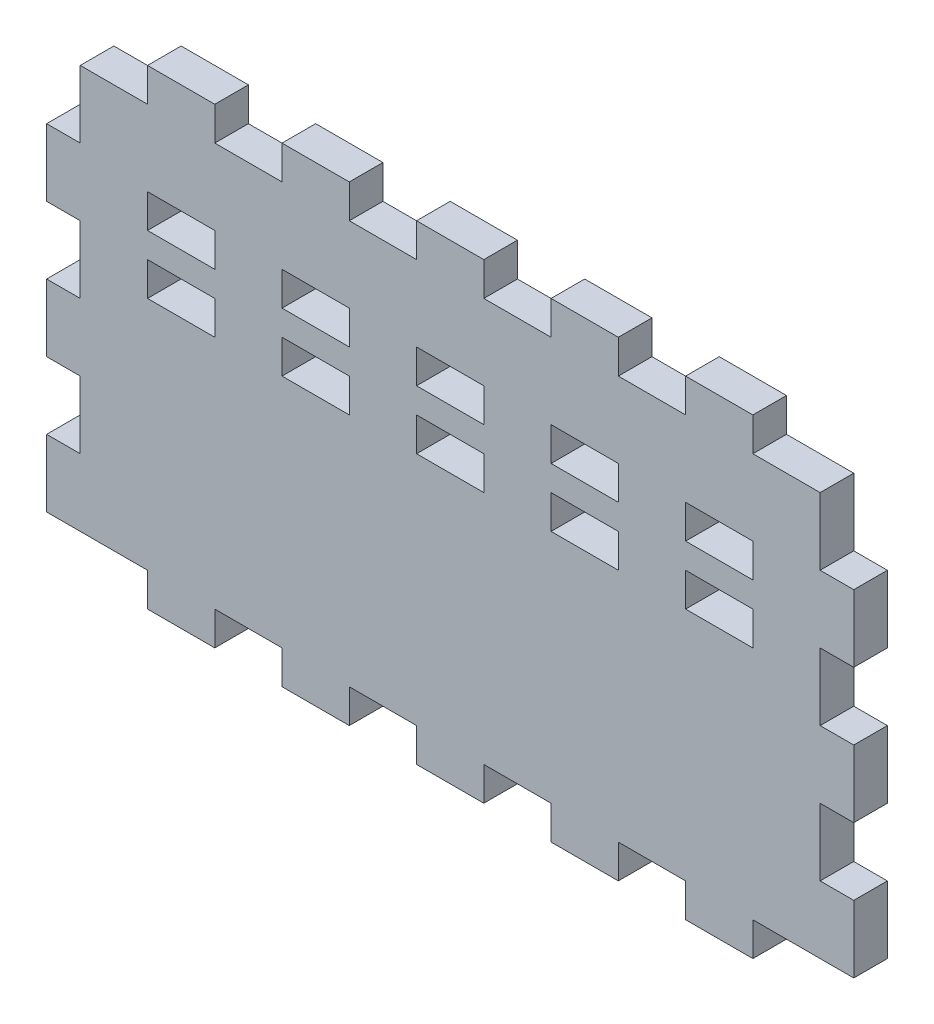
SolidWorks part; units mm, degrees
ref_plane "Front Plane" through (0, 0, 0) normal (0, 0, 1) x (1, 0, 0)
ref_plane "Top Plane" through (0, 0, 0) normal (0, 1, 0) x (1, 0, 0)
ref_plane "Right Plane" through (0, 0, 0) normal (1, 0, 0) x (0, 0, -1)
sketch "Sketch1" plane through (0, 0, 0) normal (0, 0, 1) x (1, 0, 0)
  line L1 (-139.7, -76.2) -> (139.7, -76.2)
  line L2 (-139.7, -76.2) -> (-139.7, 76.2)
  line L3 (-139.7, 76.2) -> (139.7, 76.2)
  line L4 (139.7, -76.2) -> (139.7, 76.2)
  line L5 (-139.7, -76.2) -> (139.7, 76.2) construction
  line L6 (-139.7, 76.2) -> (139.7, -76.2) construction
  point P0 (0, 0)
  dimension "D1" = 279.4
  dimension "D2" = 152.4
extrude "Boss-Extrude1" add sketch "Sketch1" along normal blind 12.7
sketch "Sketch2" plane through (0, -76.2, 0) normal (0, -1, 0) x (1, 0, 0)
  line L0 (-139.7, 0) -> (139.7, 0) construction
  line L1 (-114.3, 0) -> (-88.9, 0)
  line L2 (-114.3, 0) -> (-114.3, 12.7)
  line L3 (-114.3, 12.7) -> (-88.9, 12.7)
  line L4 (-88.9, 0) -> (-88.9, 12.7)
  line L5 (-139.7, 12.7) -> (139.7, 12.7) construction
  line L6 (-139.7, 12.7) -> (-139.7, 0) construction
  dimension "D1" = 25.4
  dimension "D2" = 25.4
extrude "Boss-Extrude2" add sketch "Sketch2" along normal blind 12.7
pattern_linear "LPattern1" count 5 spacing 50.8 along (1, 0, 0) of "Boss-Extrude2"
mirror "Mirror1" about plane through (0, 0, 0) normal (0, 1, 0) of "LPattern1"
sketch "Sketch3" plane through (139.7, 0, 0) normal (1, 0, 0) x (0, 0, -1)
  line L0 (0, 83.82) -> (0, -83.82) construction
  line L1 (-12.7, -76.2) -> (0, -76.2)
  line L2 (-12.7, -76.2) -> (-12.7, -50.8)
  line L3 (-12.7, -50.8) -> (0, -50.8)
  line L4 (0, -76.2) -> (0, -50.8)
  dimension "D1" = 25.4
extrude "Boss-Extrude3" add sketch "Sketch3" along normal blind 12.7
pattern_linear "LPattern2" count 3 spacing 50.8 along (0, 1, 0) of "Boss-Extrude3"
mirror "Mirror2" about plane through (0, 0, 0) normal (1, 0, 0) of "LPattern2"
sketch "Sketch4" plane through (0, 0, 12.7) normal (0, 0, 1) x (1, 0, 0)
  line L0 (-139.7, 25.4) -> (-139.7, 0) construction
  line L1 (-88.9, 12.7) -> (-114.3, 12.7)
  line L2 (-88.9, 12.7) -> (-88.9, 25.4)
  line L3 (-88.9, 25.4) -> (-114.3, 25.4)
  line L4 (-114.3, 12.7) -> (-114.3, 25.4)
  line L5 (-88.9, -76.2) -> (-63.5, -76.2) construction
  line L6 (-152.4, -76.2) -> (-114.3, -76.2) construction
  line L7 (-114.3, 34.925) -> (-88.9, 34.925)
  line L8 (-114.3, 34.925) -> (-114.3, 47.625)
  line L9 (-114.3, 47.625) -> (-88.9, 47.625)
  line L10 (-88.9, 34.925) -> (-88.9, 47.625)
  point P8 (-76.2, -76.2)
  dimension "D1" = 25.4
  dimension "D2" = 12.7
  dimension "D3" = 25.4
  dimension "D4" = 88.9
  dimension "D5" = 12.7
  dimension "D6" = 25.4
  dimension "D7" = 123.825
extrude "Cut-Extrude1" cut sketch "Sketch4" against normal through all
pattern_linear "LPattern3" count 5 spacing 50.8 along (1, 0, 0) of "Cut-Extrude1"
